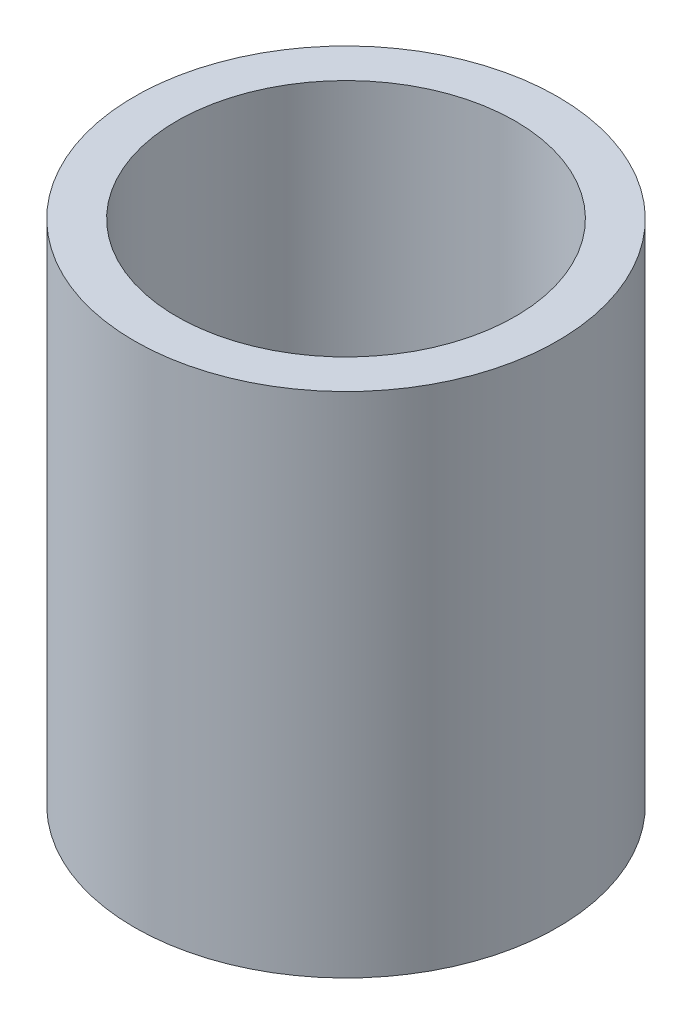
SolidWorks part; units mm, degrees
ref_plane "Front Plane" through (0, 0, 0) normal (0, 0, 1) x (1, 0, 0)
ref_plane "Top Plane" through (0, 0, 0) normal (0, 1, 0) x (1, 0, 0)
ref_plane "Right Plane" through (0, 0, 0) normal (1, 0, 0) x (0, 0, -1)
sketch "Sketch1" plane through (0, 0, 0) normal (0, 1, 0) x (1, 0, 0)
  circle A0 centre (0, 0) radius 6.35
  circle A1 centre (0, 0) radius 7.9375
  dimension "D1" = 12.7
  dimension "D2" = 15.875
extrude "Boss-Extrude1" add sketch "Sketch1" along normal blind 19.05
